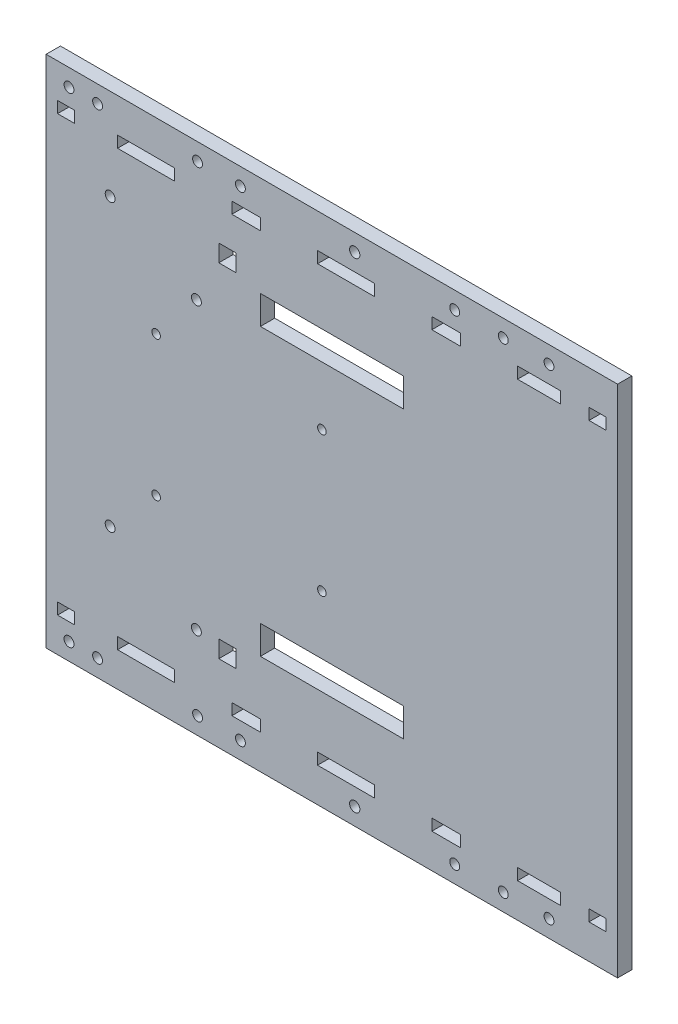
SolidWorks part; units mm, degrees
ref_plane "Front Plane" through (0, 0, 0) normal (0, 0, 1) x (1, 0, 0)
ref_plane "Top Plane" through (0, 0, 0) normal (0, 1, 0) x (1, 0, 0)
ref_plane "Right Plane" through (0, 0, 0) normal (1, 0, 0) x (0, 0, -1)
sketch "Sketch1" plane through (0, 0, 0) normal (0, 0, 1) x (1, 0, 0)
  line L1 (-100, 90) -> (100, 90)
  line L2 (-100, 90) -> (-100, -90)
  line L3 (-100, -90) -> (100, -90)
  line L4 (100, 90) -> (100, -90)
  line L5 (-100, 90) -> (100, -90) construction
  line L6 (-100, -90) -> (100, 90) construction
  point P0 (0, 0)
  dimension "D1" = 180
  dimension "D2" = 200
extrude "Boss-Extrude1" add sketch "Sketch1" along normal blind 5
sketch "Sketch3" plane through (0, 0, 5) normal (0, 0, 1) x (1, 0, 0)
  line L0 (-100, 90) -> (-100, 78)
  line L1 (-100, 90) -> (-100, -90) construction
  line L2 (-5, 78) -> (15, 78)
  line L3 (-75, 78) -> (-55, 78)
  line L5 (100, 78) -> (100, 90)
  line L6 (65, 78) -> (80, 78)
  line L7 (-75, 78) -> (-75, 74)
  line L8 (-75, 74) -> (-55, 74)
  line L9 (-55, 74) -> (-55, 78)
  line L11 (-5, 78) -> (-5, 74)
  line L12 (-5, 74) -> (15, 74)
  line L13 (15, 74) -> (15, 78)
  line L15 (65, 78) -> (65, 74)
  line L16 (65, 74) -> (80, 74)
  line L17 (80, 74) -> (80, 78)
  line L18 (80, 78) -> (65, 78)
  line L19 (-75, 78) -> (-75, 74)
  line L20 (-55, 74) -> (-55, 78)
  line L21 (-75, 78) -> (-55, 78)
  line L22 (-55, 78) -> (-55, 74)
  line L23 (-75, 78) -> (-75, 74)
  line L24 (-55, 74) -> (-75, 74)
  line L25 (-5, 78) -> (15, 78)
  line L26 (15, 74) -> (-5, 74)
  line L27 (-5, 78) -> (-5, 74)
  line L28 (15, 78) -> (-5, 78)
  line L29 (65, 78) -> (80, 78)
  line L30 (80, 74) -> (80, 78)
  line L31 (65, 74) -> (80, 74)
  line L32 (65, 78) -> (65, 74)
  line L33 (-75, 78) -> (-55, 78)
  line L34 (-5, 78) -> (15, 78)
  line L35 (65, 78) -> (80, 78)
  dimension "D1" = 12
  dimension "D4" = 25
  dimension "D5" = 4
  dimension "D6" = 20
  dimension "D7" = 4
  dimension "D8" = 50
  dimension "D9" = 4
  dimension "D10" = 20
  dimension "D11" = 4
  dimension "D12" = 50
  dimension "D13" = 4
  dimension "D14" = 15
  dimension "D15" = 4
extrude "Cut-Extrude1" cut sketch "Sketch3" against normal up to surface (5 mm away) contours L8 L9 L3 L7 up to face at (0, 0, 0)
extrude "Cut-Extrude2" cut sketch "Sketch3<6>" against normal up to surface (5 mm away) contours L2 L11 L12 L13 up to face at (-65, 76, 0)
sketch "Sketch3<6>" plane through (0, 0, 5) normal (0, 0, 1) x (1, 0, 0) same geometry as "Sketch3"
extrude "Cut-Extrude3" cut sketch "Sketch3<7>" against normal up to surface (5 mm away) contours L6 L17 L16 L15 up to face at (0, 0, 0)
sketch "Sketch3<7>" plane through (0, 0, 5) normal (0, 0, 1) x (1, 0, 0) same geometry as "Sketch3"
mirror "Mirror1" about plane through (0, 0, 0) normal (0, 1, 0) of "Cut-Extrude1", "Cut-Extrude2", "Cut-Extrude3"
sketch "Sketch5" plane through (0, 0, 5) normal (0, 0, 1) x (1, 0, 0)
  line L0 (-75, -78) -> (-75, -84)
  line L1 (-75, -84) -> (-100, -84)
  line L2 (-100, 90) -> (-100, -90) construction
  line L3 (-100, -84) -> (100, -84)
  line L4 (100, -90) -> (100, 90) construction
  line L5 (100, -84) -> (92, -84)
  line L6 (-100, -84) -> (-92, -84)
  line L7 (-92, -84) -> (-32, -84)
  line L8 (-32, -84) -> (43, -84)
  line L9 (43, -84) -> (92, -84)
  line L10 (43, -84) -> (76, -84)
  circle A1 centre (-92, -84) radius 1.73
  circle A2 centre (-32, -84) radius 1.73
  circle A3 centre (43, -84) radius 1.73
  circle A4 centre (76, -84) radius 1.73
  dimension "D3" = 33
  dimension "D5" = 3.46
  dimension "D8" = 3.46
  dimension "D9" = 3.46
  dimension "D10" = 3.46
  dimension "D1" = 6
  dimension "D2" = 8
  dimension "D4" = 8
  dimension "D6" = 60
  dimension "D7" = 75
extrude "Cut-Extrude4" cut sketch "Sketch5" against normal up to surface (5 mm away) contours A1 | A2 | A4 | A3 up to face at (5, -76, 0)
mirror "Mirror2" about plane through (0, 0, 0) normal (0, 1, 0) of "Cut-Extrude4"
sketch "Sketch6" plane through (0, 0, 5) normal (0, 0, 1) x (1, 0, 0)
  line L0 (-90, 74) -> (-96, 74)
  line L2 (-96, 74) -> (-90, 74)
  line L4 (-75, 74) -> (-55, 74)
  line L5 (-96, 74) -> (-96, 78)
  line L6 (-96, 78) -> (-90, 78)
  line L7 (-90, 78) -> (-90, 74)
  line L8 (35, 74) -> (45, 74)
  line L9 (-35, 74) -> (-35, 78)
  line L10 (-35, 78) -> (-25, 78)
  line L11 (-25, 78) -> (-25, 74)
  line L12 (-25, 74) -> (-35, 74)
  line L13 (90, 74) -> (96, 74)
  line L14 (35, 74) -> (35, 78)
  line L15 (35, 78) -> (45, 78)
  line L16 (45, 78) -> (45, 74)
  line L18 (96, 74) -> (96, 78)
  line L19 (96, 78) -> (90, 78)
  line L20 (90, 78) -> (90, 74)
  line L21 (90, 74) -> (96, 74)
  line L22 (-75, 74) -> (-55, 74)
  line L23 (-35, 74) -> (-25, 74)
  dimension "D2" = 4
  dimension "D3" = 6
  dimension "D4" = 20
  dimension "D5" = 4
  dimension "D6" = 10
  dimension "D7" = 4
  dimension "D9" = 4
  dimension "D10" = 10
  dimension "D11" = 4
  dimension "D13" = 4
  dimension "D14" = 6
  dimension "D15" = 55
  dimension "D16" = 60
  dimension "D17" = 45
extrude "Cut-Extrude5" cut sketch "Sketch6" against normal up to surface (5 mm away) contours L5 L6 L7 L0 | L11 L12 L9 L10 up to face at (-90.27, 84, 0)
extrude "Cut-Extrude6" cut sketch "Sketch6<4>" against normal up to surface (5 mm away) contours L13 L18 L19 L20 | L8 L16 L15 L14 up to face at (-30, 76, 0)
sketch "Sketch6<4>" plane through (0, 0, 5) normal (0, 0, 1) x (1, 0, 0) same geometry as "Sketch6"
mirror "Mirror3" about plane through (0, 0, 0) normal (0, 1, 0) of "Cut-Extrude5", "Cut-Extrude6"
sketch "Sketch7" plane through (0, 0, 5) normal (0, 0, 1) x (1, 0, 0)
  line L0 (-92, -84) -> (-92, -78)
  line L1 (-96, -78) -> (-90, -78) construction
  line L2 (-92, -84) -> (-82, -84)
  line L3 (-82, -84) -> (-47, -84)
  line L4 (-47, -84) -> (8, -84)
  line L5 (8, -84) -> (60, -84)
  line L6 (-82, -84) -> (-100, -84)
  line L7 (-100, 90) -> (-100, -90) construction
  circle A0 centre (-82, -84) radius 1.73
  circle A1 centre (-47, -84) radius 1.73
  circle A2 centre (8, -84) radius 1.8
  circle A3 centre (60, -84) radius 1.73
  dimension "D6" = 3.46
  dimension "D7" = 3.46
  dimension "D8" = 3.6
  dimension "D9" = 3.46
  dimension "D1" = 6
  dimension "D2" = 10
  dimension "D3" = 35
  dimension "D4" = 55
  dimension "D5" = 52
  dimension "D10" = 18
extrude "Cut-Extrude7" cut sketch "Sketch7" against normal up to surface (5 mm away) contours A3 | A2 | A1 | A0 up to face at (40, 76, 0)
mirror "Mirror4" about plane through (0, 0, 0) normal (0, 1, 0) of "Cut-Extrude7"
sketch "Sketch8" plane through (0, 0, 5) normal (0, 0, 1) x (1, 0, 0)
  line L0 (0, 90) -> (0, 55)
  line L1 (100, 90) -> (-100, 90) construction
  line L2 (-100, -90) -> (100, -90) construction
  line L3 (0, 90) -> (0, 55)
  line L5 (0, 45) -> (25, 45)
  line L6 (25, 45) -> (25, 55)
  line L7 (25, 55) -> (0, 55)
  line L8 (0, 55) -> (-25, 55)
  line L9 (-25, 55) -> (-25, 45)
  line L10 (-25, 45) -> (0, 45)
  line L11 (0, 45) -> (0, -90)
  dimension "D1" = 35
  dimension "D2" = 10
  dimension "D3" = 25
  dimension "D4" = 10
  dimension "D5" = 25
extrude "Cut-Extrude8" cut sketch "Sketch8" against normal up to surface (5 mm away) contours L5 L6 L7 L8 L9 L10 up to face at (61.73, 84, 0)
mirror "Mirror5" about plane through (0, 0, 0) normal (0, 1, 0) of "Cut-Extrude8"
sketch "Sketch9" plane through (0, 0, 5) normal (0, 0, 1) x (1, 0, 0)
  line L0 (-100, 0) -> (100, 0)
  line L1 (-100, 90) -> (-100, -90) construction
  line L2 (100, -90) -> (100, 90) construction
  line L3 (0, 0) -> (0, 24.5)
  line L4 (0, 45) -> (0, -90) construction
  line L5 (0, 24.5) -> (3.5, 24.5)
  line L6 (3.5, 24.5) -> (61.5, 24.5)
  line L7 (0, 24.5) -> (-3.5, 24.5)
  line L8 (-3.5, 24.5) -> (-61.5, 24.5)
  circle A0 centre (3.5, 24.5) radius 1.5
  circle A1 centre (61.5, 24.5) radius 1.5
  circle A2 centre (-3.5, 24.5) radius 1.5
  circle A3 centre (-61.5, 24.5) radius 1.5
  dimension "D4" = 3
  dimension "D5" = 3
  dimension "D8" = 3
  dimension "D9" = 3
  dimension "D1" = 24.5
  dimension "D2" = 3.5
  dimension "D3" = 58
  dimension "D6" = 3.5
  dimension "D7" = 58
extrude "Cut-Extrude11" cut sketch "Sketch9" against normal up to surface (5 mm away) contours A3 | A2 up to face at (93, -76, 0)
mirror "Mirror7" about plane through (0, 0, 0) normal (0, 1, 0) of "Cut-Extrude11"
sketch "Sketch10" plane through (0, 0, 5) normal (0, 0, 1) x (1, 0, 0)
  line L0 (-25, -50) -> (-100, -50)
  line L1 (-25, -55) -> (-25, -45) construction
  line L2 (-100, 90) -> (-100, -90) construction
  line L3 (-62.5, -50) -> (-77.6, -50)
  line L4 (-77.6, -50) -> (-77.6, -41.875)
  line L5 (-77.6, -41.875) -> (-47.4, -41.875)
  line L6 (-47.4, -41.875) -> (-47.4, -58.125)
  line L7 (-47.4, -58.125) -> (-77.6, -58.125)
  line L8 (-77.6, -58.125) -> (-77.6, -50)
  line L9 (-25, 50) -> (-100, 50)
  line L10 (-25, 55) -> (-25, 45) construction
  line L11 (-62.5, 50) -> (-77.6, 50)
  line L12 (-77.6, 50) -> (-77.6, 58.13)
  line L13 (-77.6, 58.13) -> (-47.4, 58.13)
  line L14 (-47.4, 58.13) -> (-47.4, 41.88)
  line L15 (-47.4, 41.88) -> (-77.6, 41.88)
  line L16 (-77.6, 41.88) -> (-77.6, 50)
  circle A0 centre (-77.6, -41.875) radius 1.73
  circle A1 centre (-47.4, -58.125) radius 1.73
  circle A2 centre (-47.4, 41.88) radius 1.73
  circle A3 centre (-77.6, 58.13) radius 1.73
  dimension "D5" = 3.46
  dimension "D6" = 3.46
  dimension "D12" = 3.46
  dimension "D13" = 3.46
  dimension "D1" = 15.1
  dimension "D2" = 8.125
  dimension "D3" = 30.2
  dimension "D4" = 16.25
  dimension "D7" = 15.1
  dimension "D8" = 8.13
  dimension "D9" = 30.2
  dimension "D10" = 16.25
  dimension "D11" = 30.2
extrude "Cut-Extrude12" cut sketch "Sketch10" against normal up to surface (5 mm away) contours A1 | A0 up to face at (-60, -24.5, 0)
extrude "Cut-Extrude13" cut sketch "Sketch10<3>" against normal up to surface (5 mm away) contours A3 | A2 up to face at (-45.67, -58.125, 0)
sketch "Sketch10<3>" plane through (0, 0, 5) normal (0, 0, 1) x (1, 0, 0) same geometry as "Sketch10"
sketch "Sketch11" plane through (0, 0, 5) normal (0, 0, 1) x (1, 0, 0)
  line L0 (-36.5665, 90) -> (-36.5665, 57)
  line L1 (100, 90) -> (-100, 90) construction
  line L3 (-36.5665, 60) -> (-36.5665, 90)
  line L4 (-39.5665, 63) -> (-33.5665, 63)
  line L5 (-39.5665, 63) -> (-39.5665, 57)
  line L6 (-39.5665, 57) -> (-33.5665, 57)
  line L7 (-33.5665, 63) -> (-33.5665, 57)
  line L8 (-39.5665, 63) -> (-33.5665, 57) construction
  line L9 (-39.5665, 57) -> (-33.5665, 63) construction
  point P6 (-36.5665, 60)
  dimension "D1" = 6
  dimension "D2" = 6
  dimension "D3" = 33
extrude "Cut-Extrude14" cut sketch "Sketch11" against normal up to surface (5 mm away) contours L4 L7 L6 L5 up to face at (-75.87, 58.13, 0)
mirror "Mirror9" about plane through (0, 0, 0) normal (0, 1, 0) of "Cut-Extrude14"
